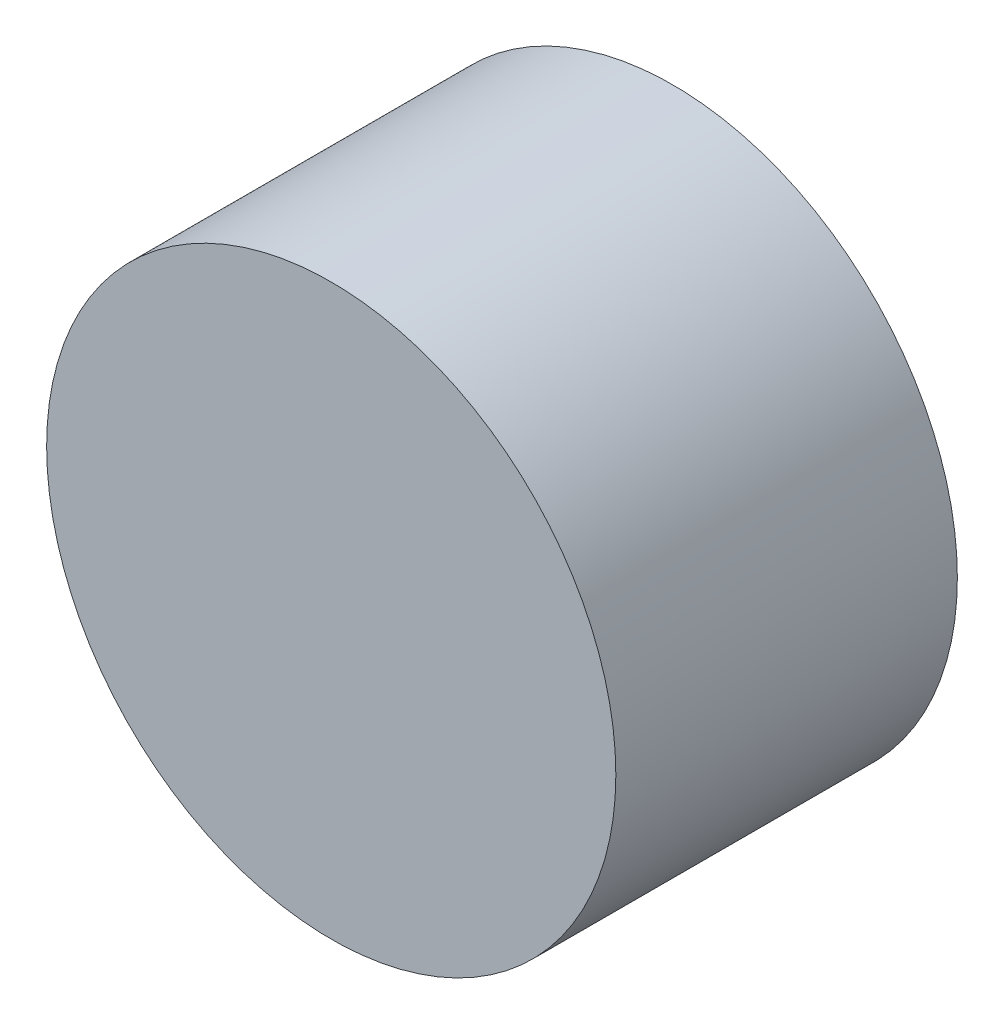
SolidWorks part; units mm, degrees
ref_plane "Front Plane" through (0, 0, 0) normal (0, 0, 1) x (1, 0, 0)
ref_plane "Top Plane" through (0, 0, 0) normal (0, 1, 0) x (1, 0, 0)
ref_plane "Right Plane" through (0, 0, 0) normal (1, 0, 0) x (0, 0, -1)
sketch "Sketch1" plane through (0, 0, 0) normal (0, 0, 1) x (1, 0, 0)
  circle A0 centre (0, 0) radius 22.5
  dimension "D1" = 45
extrude "Boss-Extrude1" add sketch "Sketch1" along normal mid plane 27
